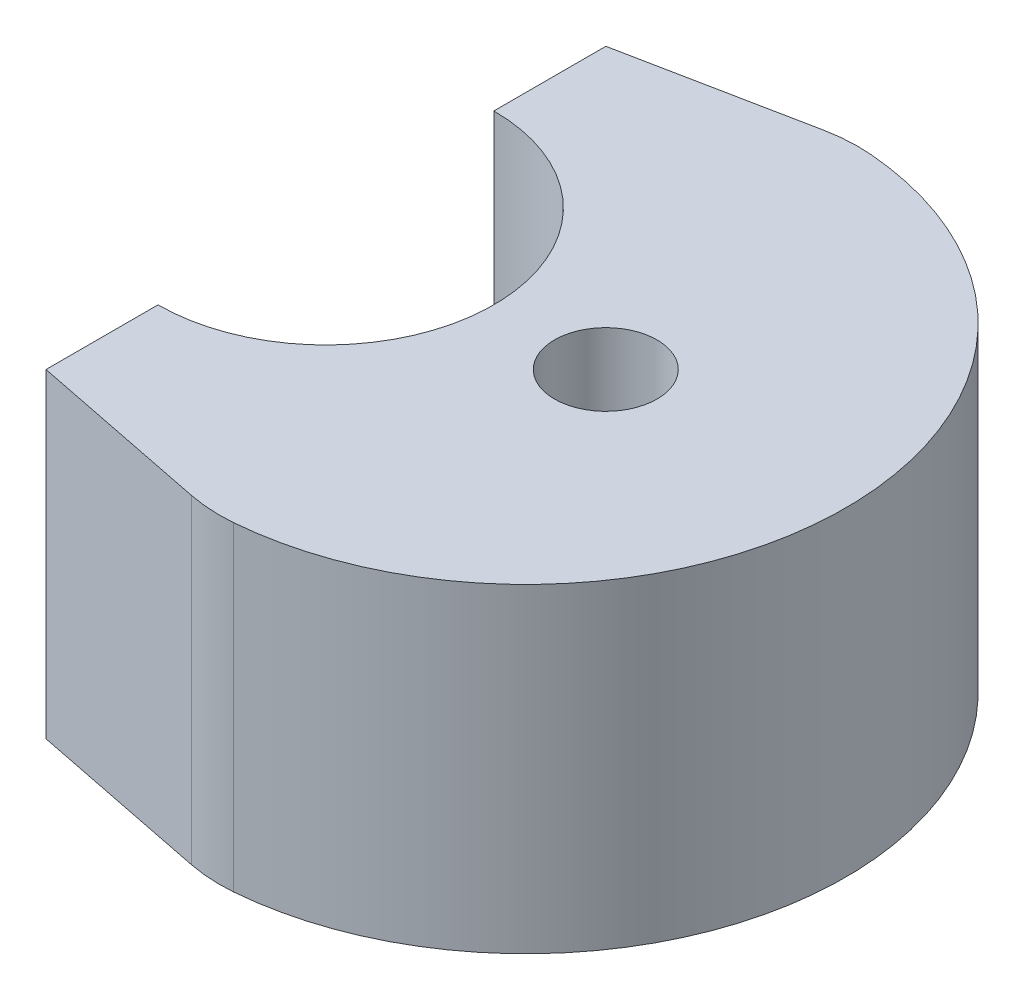
SolidWorks part; units mm, degrees
ref_plane "Front Plane" through (0, 0, 0) normal (0, 0, 1) x (1, 0, 0)
ref_plane "Top Plane" through (0, 0, 0) normal (0, 1, 0) x (1, 0, 0)
ref_plane "Right Plane" through (0, 0, 0) normal (1, 0, 0) x (0, 0, -1)
sketch "Sketch1" plane through (0, 0, 0) normal (0, 1, 0) x (1, 0, 0)
  line L0 (-0.1139, 1.9772) -> (-1.25, 1.7502)
  line L1 (-0.1139, -1.9772) -> (-1.25, -1.7502)
  line L2 (-1.25, 1.25) -> (-1.25, 1.7502)
  line L3 (-1.25, -1.25) -> (-1.25, -1.7502)
  line L4 (-1.25, -1.7502) -> (-4.1832, -1.1642)
  line L5 (-1.25, 1.7502) -> (-4.1832, 1.1642)
  line L6 (-1.25, 1.25) -> (-1.25, 1.05)
  line L7 (-1.25, -1.25) -> (-1.25, -1.05)
  circle A0 centre (-1.25, 0) radius 1.25
  circle A1 centre (-1.25, 0) radius 1.05
  arc A2 (0.1641, 1.9933) -> (0.1641, -1.9933) centre (0, 0) cw
  arc A3 (-0.1139, -1.9772) -> (0.1641, -1.9933) centre (0.0821, -0.9966) ccw
  arc A4 (-4.7783, 0.7954) -> (-4.7783, -0.7954) centre (-3.75, 0) ccw
  arc A5 (0.1641, 1.9933) -> (-0.1139, 1.9772) centre (0.0821, 0.9966) ccw
  arc A6 (-4.1832, 1.1642) -> (-4.7783, 0.7954) centre (-3.9873, 0.1835) ccw
  arc A7 (-4.1832, -1.1642) -> (-4.7783, -0.7954) centre (-3.9873, -0.1835) cw
  circle A8 centre (-3, 0) radius 0.3207
  circle A9 centre (0.5, 0) radius 0.3207
  point P12 (-3, 0)
  point P20 (0.5, 0)
extrude "Boss-Extrude1" add sketch "Sketch1" along normal blind 0.5 contours A2 A5 L0 L2 A0 L3 L1 A3 A9 region at (0.0275, 0, -1.9436)
extrude "Boss-Extrude2" add sketch "Sketch1<20>" along normal blind 1.5 from offset 0.5 contours A1 L7 A0 L6 | A2 A5 L0 L2 A0 L3 L1 A3 A9 region at (0.0275, 0, -1.9436) region at (-0.3859, 0, -0.8641)
sketch "Sketch1<20>" plane through (0, 0, 0) normal (0, 1, 0) x (1, 0, 0) same geometry as "Sketch1"
